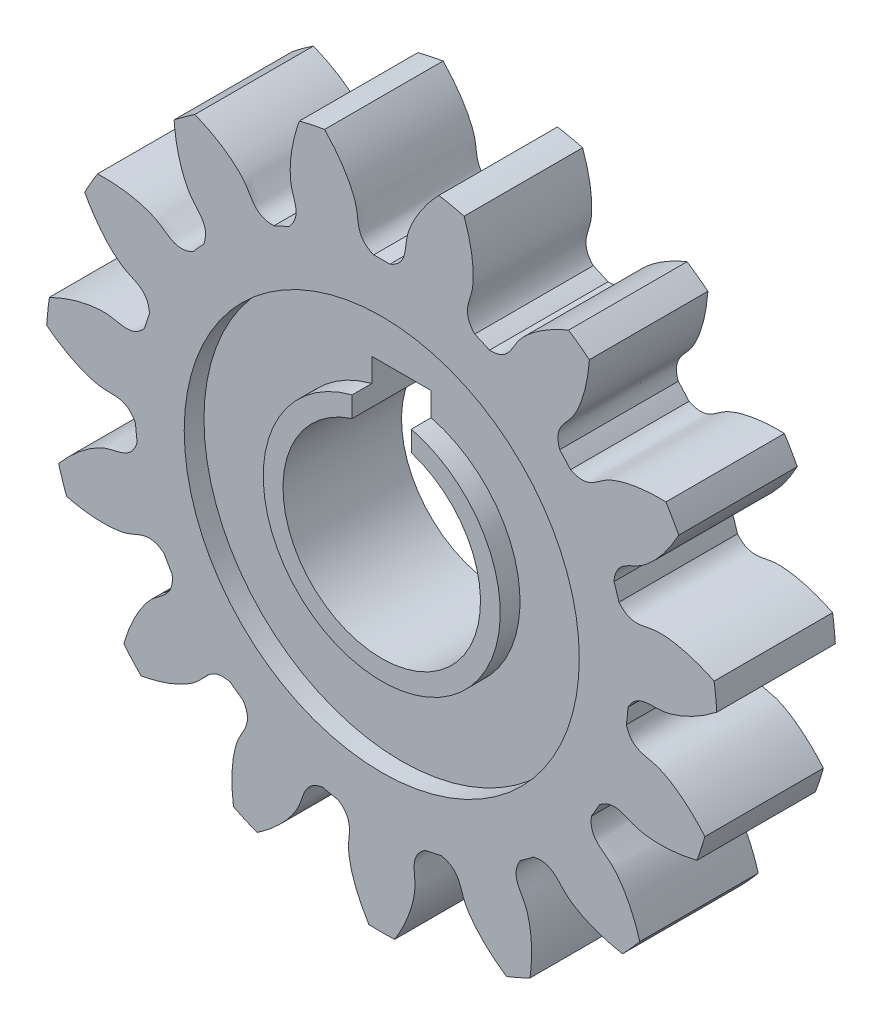
SolidWorks part; units mm, degrees
ref_plane "前视基准面" through (0, 0, 0) normal (0, 0, 1) x (1, 0, 0)
ref_plane "上视基准面" through (0, 0, 0) normal (0, 1, 0) x (1, 0, 0)
ref_plane "右视基准面" through (0, 0, 0) normal (1, 0, 0) x (0, 0, -1)
sketch "草图1" plane through (0, 0, 0) normal (0, 0, 1) x (1, 0, 0)
  circle A0 centre (0, 0) radius 17
extrude "凸台-拉伸1" add sketch "草图1" along normal blind 6
ref_axis "基准轴1" through (0, 0, -0.5) along (0, 0, 1)
sketch "草图2" plane through (0, 0, 0) normal (0, 0, 1) x (1, 0, 0)
  line L0 (0, 0) -> (0, 17) construction
  circle A0 centre (0, 0) radius 17 construction
  arc A1 (0.4086, 12.4933) -> (-0.4086, 12.4933) centre (0, 0) ccw
  arc A2 (6.4937, 19.2719) -> (-6.4937, 19.2719) centre (0, 0) ccw
  arc A3 (-6.4937, 19.2719) -> (6.4937, 19.2719) centre (0, 0) ccw construction
  spline S0 degree 3 poles (0.4086, 12.4933) (1.3144, 12.8688) (1.1442, 13.5727) (1.3025, 14.217) (1.3149, 14.2633) (1.3297, 14.3148) (1.3472, 14.3713) (1.3676, 14.4329) (1.3912, 14.4993) (1.418, 14.5705) (1.4484, 14.6465) (1.4824, 14.7269) (1.5204, 14.8119) (1.5624, 14.9011) (1.6088, 14.9946) (1.6596, 15.0921) (1.715, 15.1935) (1.7753, 15.2987) (1.8405, 15.4075) (1.9109, 15.5198) (1.9867, 15.6353) (2.0679, 15.754) (2.1547, 15.8755) (2.2473, 15.9999) (2.3459, 16.1268) (2.4505, 16.2561) (2.5613, 16.3877) (2.6784, 16.5212) (2.802, 16.6565) (2.9322, 16.7934) (3.069, 16.9316) (3.2126, 17.0711) (3.3631, 17.2115) (3.5206, 17.3526) (3.6851, 17.4942) (3.8568, 17.6361) (4.0357, 17.778) (4.2219, 17.9197) (4.4154, 18.061) (4.6163, 18.2017) (4.8247, 18.3414) (5.0406, 18.48) (5.2641, 18.6172) (5.4951, 18.7527) (5.7336, 18.8864) (6.0652, 19.0635) (6.3203, 19.1901) (6.4937, 19.2719) knots 0 0 0 0 0.202473 0.206979 0.212085 0.217793 0.224101 0.23101 0.23852 0.24663 0.255341 0.264653 0.274566 0.285079 0.296194 0.307909 0.320225 0.333141 0.346659 0.360777 0.375496 0.390816 0.406736 0.423257 0.440379 0.458102 0.476426 0.49535 0.514875 0.535001 0.555728 0.577055 0.598984 0.621513 0.644642 0.668373 0.692704 0.717636 0.743169 0.769303 0.796037 0.823373 0.851309 0.879845 0.908983 0.938721 1 1 1 1
  spline S1 degree 3 poles (-0.4086, 12.4933) (-1.3144, 12.8688) (-1.1442, 13.5727) (-1.3025, 14.217) (-1.3149, 14.2633) (-1.3297, 14.3148) (-1.3472, 14.3713) (-1.3676, 14.4329) (-1.3912, 14.4993) (-1.418, 14.5705) (-1.4484, 14.6465) (-1.4824, 14.7269) (-1.5204, 14.8119) (-1.5624, 14.9011) (-1.6088, 14.9946) (-1.6596, 15.0921) (-1.715, 15.1935) (-1.7753, 15.2987) (-1.8405, 15.4075) (-1.9109, 15.5198) (-1.9867, 15.6353) (-2.0679, 15.754) (-2.1547, 15.8755) (-2.2473, 15.9999) (-2.3459, 16.1268) (-2.4505, 16.2561) (-2.5613, 16.3877) (-2.6784, 16.5212) (-2.802, 16.6565) (-2.9322, 16.7934) (-3.069, 16.9316) (-3.2126, 17.0711) (-3.3631, 17.2115) (-3.5206, 17.3526) (-3.6851, 17.4942) (-3.8568, 17.6361) (-4.0357, 17.778) (-4.2219, 17.9197) (-4.4154, 18.061) (-4.6163, 18.2017) (-4.8247, 18.3414) (-5.0406, 18.48) (-5.2641, 18.6172) (-5.4951, 18.7527) (-5.7336, 18.8864) (-6.0652, 19.0635) (-6.3203, 19.1901) (-6.4937, 19.2719) knots 0 0 0 0 0.202473 0.206979 0.212085 0.217793 0.224101 0.23101 0.23852 0.24663 0.255341 0.264653 0.274566 0.285079 0.296194 0.307909 0.320225 0.333141 0.346659 0.360777 0.375496 0.390816 0.406736 0.423257 0.440379 0.458102 0.476426 0.49535 0.514875 0.535001 0.555728 0.577055 0.598984 0.621513 0.644642 0.668373 0.692704 0.717636 0.743169 0.769303 0.796037 0.823373 0.851309 0.879845 0.908983 0.938721 1 1 1 1
extrude "切除-拉伸1" cut sketch "草图2" along normal through all
pattern_circular "阵列(圆周)1" count 15 every 24 about axis through (0, 0, -0.5) along (0, 0, 1) of "切除-拉伸1"
sketch "草图3" plane through (0, 0, 0) normal (0, 0, 1) x (1, 0, 0)
  circle A0 centre (0, 0) radius 15 construction
  dimension "Dn" = 30
sketch "草图4" plane through (0, 0, 6) normal (0, 0, 1) x (1, 0, 0)
  line L0 (-1.5, 3) -> (-1.5, 4.7697) construction
  line L1 (-1.5, 3) -> (1.5, 3) construction
  line L2 (-1.5, 4.7697) -> (-1.5, 7)
  line L3 (-1.5, 7) -> (1.5, 7)
  line L4 (1.5, 4.7697) -> (1.5, 7)
  line L5 (-1.5, 3) -> (1.5, 7) construction
  line L6 (-1.5, 7) -> (1.5, 3) construction
  line L7 (1.5, 3) -> (1.5, 4.7697) construction
  arc A0 (-1.5, 4.7697) -> (1.5, 4.7697) centre (0, 0) ccw
  arc A1 (1.5, 4.7697) -> (0, 5) centre (0, 0) ccw construction
  arc A2 (0, 5) -> (-1.5, 4.7697) centre (0, 0) ccw construction
  point P3 (0, 5)
  dimension "D1" = 10
  dimension "D2" = 4
  dimension "D3" = 3
extrude "切除-拉伸2" cut sketch "草图4" against normal up to next
sketch "草图5" plane through (0, 0, 6) normal (0, 0, 1) x (1, 0, 0)
  circle A0 centre (0, 0) radius 10
  circle A1 centre (0, 0) radius 6
  arc A2 (-1.5, 4.7697) -> (1.5, 4.7697) centre (0, 0) ccw construction
  dimension "D1" = 20
  dimension "D2" = 1
extrude "切除-拉伸3" cut sketch "草图5" against normal blind 1
